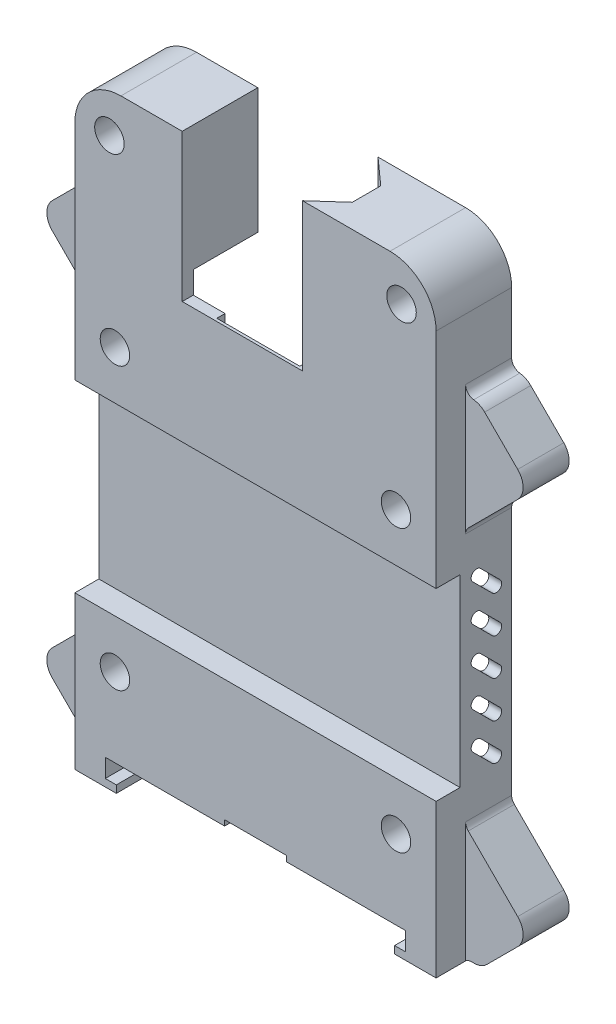
SolidWorks part; units mm, degrees
ref_plane "Front Plane" through (0, 0, 0) normal (0, 0, 1) x (1, 0, 0)
ref_plane "Top Plane" through (0, 0, 0) normal (0, 1, 0) x (1, 0, 0)
ref_plane "Right Plane" through (0, 0, 0) normal (1, 0, 0) x (0, 0, -1)
sketch "Sketch3" plane through (0, 0, 0) normal (0, 0, 1) x (1, 0, 0)
  line L0 (-18, 23) -> (18, 23)
  line L1 (-18, -23) -> (18, -23)
  line L2 (-18, -23) -> (-18, 23)
  line L3 (-19.6, 39.2) -> (19.6, 39.2)
  line L4 (18, -23) -> (18, 23)
  line L5 (-19.6, 0) -> (19.6, 0) construction
  line L6 (-7.85, 39.2) -> (-7.85, 23)
  line L7 (15.25, -15.25) -> (-15.25, -15.25) construction
  line L8 (4.95, 39.2) -> (4.95, 23)
  line L9 (0, 39.2) -> (0, -24.6) construction
  line L10 (19.6, -24.6) -> (19.6, 39.2)
  line L11 (-19.6, -24.6) -> (19.6, -24.6)
  line L12 (-19.6, -24.6) -> (-19.6, 39.2)
  line L13 (15.25, -15.25) -> (15.25, 15.25) construction
  line L14 (15.25, 15.25) -> (-15.25, 15.25) construction
  line L15 (-15.25, -15.25) -> (-15.25, 15.25) construction
  line L16 (15.25, -15.25) -> (-15.25, 15.25) construction
  line L17 (15.25, 15.25) -> (-15.25, -15.25) construction
  line L18 (-18, -23) -> (-18, 39.2) construction
  line L19 (18, -23) -> (18, 39.2) construction
  line L20 (-18.2, 23.2) -> (18.2, 23.2)
  line L21 (18.2, -23.2) -> (18.2, 23.2)
  line L22 (-18.2, -23.2) -> (18.2, -23.2)
  line L23 (-18.2, -23.2) -> (-18.2, 23.2)
  line L24 (-15.25, 18.2) -> (-18.2, 18.2)
  line L25 (-15.25, 12.3) -> (-18.2, 12.3)
  line L26 (15.25, 12.3) -> (18.2, 12.3)
  line L27 (15.25, 18.2) -> (18.2, 18.2)
  line L28 (15.25, -12.3) -> (18.2, -12.3)
  line L29 (15.25, -18.2) -> (18.2, -18.2)
  line L30 (-15.25, -12.3) -> (-18.2, -12.3)
  line L31 (-15.25, -18.2) -> (-18.2, -18.2)
  circle A4 centre (-15.25, 15.25) radius 2.95
  circle A5 centre (15.25, 15.25) radius 2.95
  circle A6 centre (15.25, -15.25) radius 2.95
  circle A7 centre (-15.25, -15.25) radius 2.95
  point P21 (0, 0)
  dimension "D3" = 36
  dimension "D4" = 46
  dimension "D5" = 39.2
  dimension "D6" = 0.2
  dimension "D1" = 1.6
extrude "Base body" add sketch "Sketch3" along normal up to surface (8.2 mm away) contours L22 L23 L20 L6 L3 L12 L11 L10 L21 | A4 L24 L2 | A4 L2 | A4 L2 L25 | L27 A5 L4 | L4 A5 L26 | A5 L4 | L4 A6 | A6 L4 L28 | A6 L29 L4 | A7 L2 | L2 A7 L30 | L31 A7 L2 | L23 A7 L2 L30 | A7 L2 | L2 A7 L23 L31 | A4 L2 L24 L23 | L2 A4 | A4 L23 L25 L2 | L4 A5 L21 L27 | A5 L4 | L21 A5 L4 L26 | A6 L21 L28 L4 | A6 L4 | A6 L4 L29 L21 region at (-17.3634, 17.6894, 0) region at (-18.1063, 17.0693, 0) region at (-13.025, 23.9488, 0) region at (-15.22, 15.25, 0) region at (-18.0802, 15.25, 0) region at (-17.3634, 12.8106, 0) region at (-18.1063, 13.4307, 0) region at (18.1063, 17.0693, 0) region at (17.3634, 17.6894, 0) region at (18.0802, 15.25, 0) region at (15.22, 15.25, 0) region at (-17.3634, -12.8106, 0) region at (-18.1063, -13.4307, 0) region at (18.1063, 13.4307, 0) region at (17.3634, 12.8106, 0) region at (-15.22, -15.25, 0) region at (-18.0802, -15.25, 0) region at (-18.1063, -17.0693, 0) region at (-17.3634, -17.6894, 0) region at (18.1063, -13.4307, 0) region at (17.3634, -12.8106, 0) region at (18.0802, -15.25, 0) region at (15.22, -15.25, 0) region at (18.1063, -17.0693, 0) region at (17.3634, -17.6894, 0)
sketch "Sketch5" plane through (0, 0, 0) normal (0, 0, -1) x (-1, 0, 0)
  line L1 (-18.2, 23.2) -> (18.2, 23.2)
  line L2 (-18.2, 23.2) -> (-18.2, -23.2)
  line L3 (-18.2, -23.2) -> (18.2, -23.2)
  line L4 (18.2, 23.2) -> (18.2, -23.2)
extrude "PCB cut" cut sketch "Sketch5" against normal up to surface (1.95 mm away)
sketch "Sketch7" plane through (-18.2, 0, 0) normal (1, 0, 0) x (0, 0, -1)
  line L0 (-8.2, 23.2) -> (0, 23.2) construction
  line L1 (-8.2, -23.2) -> (-7, -23.2)
  line L2 (-8.2, -23.2) -> (-8.2, 23.2)
  line L3 (-8.2, 23.2) -> (-7, 23.2)
  line L4 (-7, -23.2) -> (-7, 23.2)
  line L5 (-4.6, 0) -> (-8.2, 0) construction
  line L6 (-8.2, -11) -> (-4.6, -11)
  line L7 (-8.2, -11) -> (-8.2, 11)
  line L8 (-8.2, 11) -> (-4.6, 11)
  line L9 (-4.6, -11) -> (-4.6, 11)
  line L10 (-7, 0) -> (-8.2, 0) construction
  dimension "D1" = 22
  dimension "D2" = 1.2
  dimension "D3" = 3.6
extrude "Bottom" add sketch "Sketch7" along normal up to surface (36.4 mm away) contours L4 L3 L2 L1 | L6 L9 L8 L7 up to face at (18.2, 0, 4.75)
sketch "Sketch25" plane through (0, 0, 7) normal (0, 0, -1) x (-1, 0, 0)
  line L0 (19.6, 0) -> (-19.6, 0) construction
  line L1 (0, 39.2) -> (0, -24.6) construction
  line L2 (19.6, 0) -> (-19.6, 0)
  line L3 (0, 39.2) -> (0, -24.6)
  circle A0 centre (-15.25, 15.25) radius 1.6
  circle A2 centre (15.25, 15.25) radius 1.6
  circle A3 centre (15.25, -15.25) radius 1.6
  circle A4 centre (-15.25, -15.25) radius 1.6
  circle A5 centre (-15.85, 34.85) radius 1.6
  circle A6 centre (15.85, 34.85) radius 1.6
  circle A10 centre (-15.25, 15.25) radius 1.6 construction
  circle A11 centre (-15.85, 34.85) radius 1.6 construction
  circle A12 centre (15.85, 34.85) radius 1.6 construction
extrude "Hole cut" cut sketch "Sketch25" against normal up to next and the other way up to next contours A0 | A2 | A4 | A3 | A6 | A5 region at (15.25, 15.25, 7) region at (-15.25, 15.25, 7) region at (-15.25, -15.25, 7) region at (15.25, -15.25, 7) region at (15.85, 34.85, 7) region at (-15.85, 34.85, 7)
sketch "Sketch9" plane through (-18.2, 0, 0) normal (1, 0, 0) x (0, 0, -1)
  line L11 (-8.2, 10) -> (-8.2, -10)
  line L14 (-8.2, 10) -> (-5.6, 10)
  line L15 (-5.6, 10) -> (-5.6, -10)
  line L16 (-5.6, -10) -> (-8.2, -10)
  line L17 (-8.2, 10) -> (-5.6, 10)
  line L18 (-5.6, 10) -> (-5.6, -10)
  line L19 (-5.6, -10) -> (-8.2, -10)
  dimension "D1" = 1
extrude "Battery strap cut" cut sketch "Sketch9" along normal up to next and the other way up to next
sketch "Sketch11" plane through (0, -24.6, 0) normal (0, -1, 0) x (1, 0, 0)
  line L0 (-19.6, 0) -> (19.6, 0) construction
  line L1 (15.1, 0) -> (15.1, 8.2)
  line L2 (19.6, 8.2) -> (19.6, 0) construction
  line L3 (-19.6, 8.2) -> (-19.6, 0)
  line L4 (-19.6, 8.2) -> (-15.1, 8.2)
  line L6 (0, 8.2) -> (0, 0) construction
  line L7 (19.6, 8.2) -> (-19.6, 8.2) construction
  line L8 (-15.1, 0) -> (-15.1, 8.2)
  line L9 (19.6, 0) -> (15.1, 0)
  line L10 (19.6, 8.2) -> (19.6, 0)
  line L11 (19.6, 8.2) -> (15.1, 8.2)
  line L12 (-19.6, 0) -> (-15.1, 0)
  line M6 (19.6, 0) -> (19.6, 8.2)
  line M7 (19.6, 8.2) -> (-19.6, 8.2)
  line M8 (-19.6, 8.2) -> (-19.6, 0)
  line M9 (-19.6, 0) -> (19.6, 0)
  dimension "D1" = 4.5
extrude "Led strip holder" add sketch "Sketch11" along normal blind 2 contours M8 M9 | M7 M9 M6 region at (17.35, -24.6, 4.1) region at (-17.35, -24.6, 4.1)
sketch "Sketch14" plane through (0, 0, 8.2) normal (0, 0, 1) x (1, 0, 0)
  line L0 (-16.3, -23.8) -> (16.3, -23.8)
  line L1 (-16.1, -24) -> (16.1, -24)
  line L2 (-16.1, -24) -> (-16.1, -25.6)
  line L3 (-16.1, -25.6) -> (16.1, -25.6)
  line L4 (16.1, -24) -> (16.1, -25.6)
  line L5 (16.3, -23.8) -> (16.3, -25.8)
  line L6 (-16.3, -25.8) -> (16.3, -25.8)
  line L7 (-16.3, -23.8) -> (-16.3, -25.8)
  dimension "D1" = 0.2
extrude "Led strip cut" cut sketch "Sketch14" against normal up to next contours L5 L6 L7 L0
sketch "Sketch15" plane through (0, -23.8, 0) normal (0, -1, 0) x (1, 0, 0)
  line L0 (0, 8.2) -> (0, 0) construction
  line L1 (0, 8.2) -> (0, 0) construction
  circle A0 centre (-8, 1.35) radius 1
  circle A1 centre (-8, 1.35) radius 1 construction
  circle A2 centre (-8, 1.35) radius 0.8
  circle A3 centre (8, 1.35) radius 0.8
  dimension "D1" = 0.2
extrude "Led strip hole holder" add sketch "Sketch15" along normal blind 0.7 contours A2 | A3 region at (-8, -23.8, 1.35) region at (8, -23.8, 1.35)
sketch "Sketch20" plane through (0, -23.2, 0) normal (0, 1, 0) x (1, 0, 0)
  line L0 (0, -7) -> (0, 0) construction
  line L1 (18.2, -7) -> (-18.2, -7) construction
  line L2 (-18.2, 0) -> (18.2, 0) construction
  line L3 (4, -4.7) -> (-4, -4.7) construction
  line L4 (4, -6.2998) -> (-4, -6.2998)
  line L5 (4, -3.1002) -> (-4, -3.1002)
  arc A0 (4, -6.2998) -> (4, -3.1002) centre (4, -4.7) ccw
  arc A1 (-4, -3.1002) -> (-4, -6.2998) centre (-4, -4.7) ccw
  point P8 (0, -4.7)
  dimension "D3" = 1.5998
  dimension "D1" = 8
  dimension "D2" = 4.7
extrude "Led strip wire hole" cut sketch "Sketch20" against normal up to next
sketch "Sketch16" plane through (0, 39.2, 0) normal (0, 1, 0) x (1, 0, 0)
  line L0 (-7.95, 0) -> (5.0998, 0)
  line L1 (4.95, 0) -> (7.85, -2.6)
  line L2 (-7.95, -8.2) -> (-7.95, 0)
  line L3 (-7.95, -8.2) -> (-7.95, 0)
  line L4 (7.85, -2.6) -> (7.85, -5.6)
  line L5 (7.85, -5.6) -> (4.95, -8.2)
  line L6 (5.0998, -8.2) -> (-7.95, -8.2)
  line L7 (5.0998, 0) -> (7.95, -2.5553)
  line L8 (7.95, -2.5553) -> (7.95, -5.6447)
  line L9 (7.95, -5.6447) -> (5.0998, -8.2)
  line L10 (5.0168, 0.0745) -> (7.95, -2.5553) construction
  line L11 (7.95, -5.6447) -> (5.0168, -8.2745) construction
  line L12 (4.95, 0) -> (19.6, 0) construction
  line L14 (19.6, -8.2) -> (4.95, -8.2) construction
  dimension "D1" = 0.1
  dimension "D2" = 0.1
extrude "XT60 cut" cut sketch "Sketch16" against normal up to surface (16 mm away) contours L7 L8 L9 L6 L3 L0 up to face at (-13.025, 23.2, 3.5)
sketch "Sketch21" plane through (0, 0, 0) normal (0, 0, -1) x (-1, 0, 0)
  line L0 (18.2, 23.2) -> (-18.2, 23.2) construction
  line L1 (9.35, 23.2) -> (18.2, 23.2)
  line L2 (9.35, 23.2) -> (9.35, 32.2)
  line L3 (9.35, 32.2) -> (18.2, 32.2)
  line L4 (18.2, 23.2) -> (18.2, 32.2)
  line L5 (0, 39.2) -> (0, -24.6) construction
  line L6 (0, 39.2) -> (0, -24.6) construction
  line L7 (-18.2, 23.2) -> (-18.2, 32.2)
  line L8 (-9.35, 32.2) -> (-18.2, 32.2)
  line L9 (-9.35, 23.2) -> (-9.35, 32.2)
  line L10 (-9.35, 23.2) -> (-18.2, 23.2)
  line L11 (18.2, 32.2) -> (19.6, 32.2) construction
  line L13 (19.6, -24.6) -> (19.6, 39.2) construction
  line L14 (9.35, 32.2) -> (7.95, 32.2) construction
  line L15 (7.95, 23.2) -> (7.95, 39.2) construction
  line L16 (18.2, -23.2) -> (18.2, 23.2) construction
  dimension "D2" = 9
extrude "Wire pocket" cut sketch "Sketch21" against normal up to surface (7 mm away) up to face at (-0.108, 16.9143, 7)
sketch "Sketch22" plane through (0, 0, 0) normal (0, 0, 1) x (1, 0, 0)
  line L0 (0, 39.2) -> (0, -23.8) construction
  line L1 (-7.85, 39.2) -> (4.95, 39.2) construction
  line L2 (-16.3, -23.8) -> (16.3, -23.8) construction
  line L3 (-19.6, 0) -> (19.6, 0) construction
  line L4 (-19.6, -10) -> (-19.6, 10) construction
  line L5 (19.6, 10) -> (19.6, -10) construction
  line L6 (-19.6, 13.9431) -> (-26.6711, 21.0142)
  line L7 (-19.6, 39.2) -> (-19.6, 10) construction
  line L8 (-26.6711, 21.0142) -> (-21.0142, 26.6711)
  line L9 (-21.0142, 26.6711) -> (-19.6, 25.2569)
  line L10 (-19.6, 25.2569) -> (-19.6, 13.9431)
  line L14 (-23.8426, 23.8426) -> (-19.6, 19.6) construction
  dimension "D1" = 45
  dimension "D2" = 10
  dimension "D3" = 8
extrude "ESC wire extrude" add sketch "Sketch22" along normal blind 5
sketch "Sketch23" plane through (0, 0, 0) normal (0, 0, -1) x (-1, 0, 0)
  line L0 (18.2, 24.4083) -> (18.2, 18.2)
  line L6 (20.4485, 24.4083) -> (18.2, 24.4083)
  line L7 (18.2, -23.2) -> (18.2, 32.2) construction
  line L8 (18.2, 18.2) -> (22.1598, 18.2)
  line L9 (20.4485, 24.4083) -> (21.0142, 24.974)
  line L10 (24.974, 21.0142) -> (18.7515, 14.7917)
  line L11 (21.0142, 24.974) -> (24.974, 21.0142)
  line L12 (20.4485, 24.4083) -> (21.0142, 24.974)
  line L13 (24.974, 21.0142) -> (22.1598, 18.2)
  line L14 (21.0142, 24.974) -> (24.974, 21.0142)
  dimension "D1" = 1.2
extrude "ESC wire pocket" cut sketch "Sketch23" against normal offset from surface (3.8 mm away) 1.2 up to face at (-21.7213, 21.7213, 5)
mirror "Mirror left-right" about plane through (0, 0, 0) normal (1, 0, 0) of "ESC wire extrude", "ESC wire pocket"
mirror "Mirror top-bottom" about plane through (0, 0, 0) normal (0, 1, 0) of "Mirror left-right"
fillet "Inner fillet" radius 2 6 edges at (-18.2, 21.3042, 3.8) (-18.2, 24.4083, 1.9) (18.2, 24.4083, 1.9) (18.2, 21.3042, 3.8) (18.2, -20.7, 3.8) (-18.2, -20.7, 3.8)
fillet "Outer fillet" radius 1 8 edges at (-19.6, 25.2569, 2.5) (-19.6, 13.9431, 2.5) (19.6, 13.9431, 2.5) (19.6, -13.9431, 2.5) (-19.6, -13.9431, 2.5) (19.6, -25.2569, 2.5) (-19.6, -25.2569, 2.5) (19.6, 25.2569, 2.5)
fillet "Fillet2" radius 2 8 edges at (-21.0142, 26.6711, 2.5) (-26.6711, 21.0142, 2.5) (-26.6711, -21.0142, 2.5) (-21.0142, -26.6711, 2.5) (21.0142, -26.6711, 2.5) (26.6711, -21.0142, 2.5) (21.0142, 26.6711, 2.5) (26.6711, 21.0142, 2.5)
sketch "Sketch24" plane through (-19.6, 0, 0) normal (-1, 0, 0) x (0, 0, 1)
  line L0 (4.1, 39.2) -> (4.1, -26.351) construction
  line L1 (8.2, 39.2) -> (0, 39.2) construction
  line L3 (3.8, 9.0607) -> (1.6787, 6.9393) construction
  line L4 (4.221, 8.6397) -> (2.0997, 6.5184)
  line L5 (3.379, 9.4816) -> (1.2577, 7.3603)
  line L6 (3.8, 5.0607) -> (1.6787, 2.9393) construction
  line L7 (4.221, 4.6397) -> (2.0997, 2.5184)
  line L8 (3.379, 5.4816) -> (1.2577, 3.3603)
  line L9 (3.8, 1.0607) -> (1.6787, -1.0607) construction
  line L10 (4.221, 0.6397) -> (2.0997, -1.4816)
  line L11 (3.379, 1.4816) -> (1.2577, -0.6397)
  line L12 (3.8, -2.9393) -> (1.6787, -5.0607) construction
  line L13 (4.221, -3.3603) -> (2.0997, -5.4816)
  line L14 (3.379, -2.5184) -> (1.2577, -4.6397)
  line L15 (3.8, -6.9393) -> (1.6787, -9.0607) construction
  line L16 (4.221, -7.3603) -> (2.0997, -9.4816)
  line L17 (3.379, -6.5184) -> (1.2577, -8.6397)
  line L18 (5.6, 0) -> (0, 0) construction
  line L19 (5.6, -10) -> (5.6, 10) construction
  line L20 (0, -13.5289) -> (0, 13.5289) construction
  line L21 (3.8, -6.9393) -> (3.8, 9.0607) construction
  line L22 (0, -26.351) -> (5, -26.351) construction
  arc A0 (4.221, 8.6397) -> (3.379, 9.4816) centre (3.8, 9.0607) ccw
  arc A1 (1.2577, 7.3603) -> (2.0997, 6.5184) centre (1.6787, 6.9393) ccw
  arc A2 (4.221, 4.6397) -> (3.379, 5.4816) centre (3.8, 5.0607) ccw
  arc A3 (1.2577, 3.3603) -> (2.0997, 2.5184) centre (1.6787, 2.9393) ccw
  arc A4 (4.221, 0.6397) -> (3.379, 1.4816) centre (3.8, 1.0607) ccw
  arc A5 (1.2577, -0.6397) -> (2.0997, -1.4816) centre (1.6787, -1.0607) ccw
  arc A6 (4.221, -3.3603) -> (3.379, -2.5184) centre (3.8, -2.9393) ccw
  arc A7 (1.2577, -4.6397) -> (2.0997, -5.4816) centre (1.6787, -5.0607) ccw
  arc A8 (4.221, -7.3603) -> (3.379, -6.5184) centre (3.8, -6.9393) ccw
  arc A9 (1.2577, -8.6397) -> (2.0997, -9.4816) centre (1.6787, -9.0607) ccw
  point P8 (2.7393, 8)
  point P17 (2.7393, 4)
  point P24 (2.7393, 0)
  point P31 (2.7393, -4)
  point P38 (2.7393, -8)
  dimension "D1" = 0.5954
  dimension "D2" = 45
  dimension "D3" = 3
  dimension "D5" = 4
  dimension "D6" = 0.3
  dimension "D4" = 5
extrude "Ventilation cut" cut sketch "Sketch24" against normal through all both and the other way through all
fillet "Fillet1" radius 5 2 edges at (19.6, 39.2, 4.1) (-19.6, 39.2, 4.1)
sketch "Sketch26" plane through (0, 0, 0) normal (0, 0, -1) x (-1, 0, 0)
  line L0 (-9.35, 23.2) -> (-9.35, 32.2) construction
  line L1 (-9.35, 25.6) -> (9.35, 25.6)
  line L2 (-9.35, 25.6) -> (-9.35, 23.2)
  line L3 (-9.35, 23.2) -> (9.35, 23.2)
  line L4 (9.35, 25.6) -> (9.35, 23.2)
  line L5 (-9.35, 25.6) -> (9.35, 23.2) construction
  line L6 (-9.35, 23.2) -> (9.35, 25.6) construction
  point P4 (0, 24.4)
  dimension "D1" = 2.4
extrude "Capacitor cut" cut sketch "Sketch26" against normal up to surface (7 mm away) up to face at (-0.084, 20.3111, 7)
sketch "Sketch27" plane through (0, 0, 7) normal (0, 0, -1) x (-1, 0, 0)
  line L0 (-6.4383, 23.2) -> (7.95, 23.2) construction
  line L1 (-4.5, 23.2) -> (4.5, 23.2)
  line L2 (-4.5, 23.2) -> (-4.5, 11.6)
  line L3 (-4.5, 11.6) -> (4.5, 11.6)
  line L4 (4.5, 23.2) -> (4.5, 11.6)
  line L5 (-4.5, 23.2) -> (4.5, 11.6) construction
  line L6 (-4.5, 11.6) -> (4.5, 23.2) construction
  line L7 (-9.35, 25.6) -> (9.35, 25.6) construction
  line L9 (0, 25.6) -> (0, 11.6) construction
  point P4 (0, 17.4)
  point P11 (0, 0)
  dimension "D1" = 11.6
  dimension "D2" = 9
extrude "Cut-Extrude2" cut sketch "Sketch27" against normal offset from surface (0.9 mm away) 0.3 up to face at (13.65, -15.25, 8.2)
sketch "Sketch28" plane through (0, 0, 8.2) normal (0, 0, 1) x (1, 0, 0)
  line L0 (-16.3, -23.8) -> (16.3, -23.8) construction
  line L1 (-3.35, -23.8) -> (3.35, -23.8)
  line L2 (-3.35, -23.8) -> (-3.35, -23.2)
  line L3 (-3.35, -23.2) -> (3.35, -23.2)
  line L4 (3.35, -23.8) -> (3.35, -23.2)
  line L5 (-3.35, -23.8) -> (3.35, -23.2) construction
  line L6 (-3.35, -23.2) -> (3.35, -23.8) construction
  line L7 (0, -10) -> (0, -23.8) construction
  line L8 (-19.6, -10) -> (19.6, -10) construction
  line L9 (18.2, -23.2) -> (-18.2, -23.2) construction
  point P4 (0, -23.5)
  point P12 (0, 0)
  dimension "D1" = 6.7
extrude "Cut-Extrude3" cut sketch "Sketch28" against normal up to next
